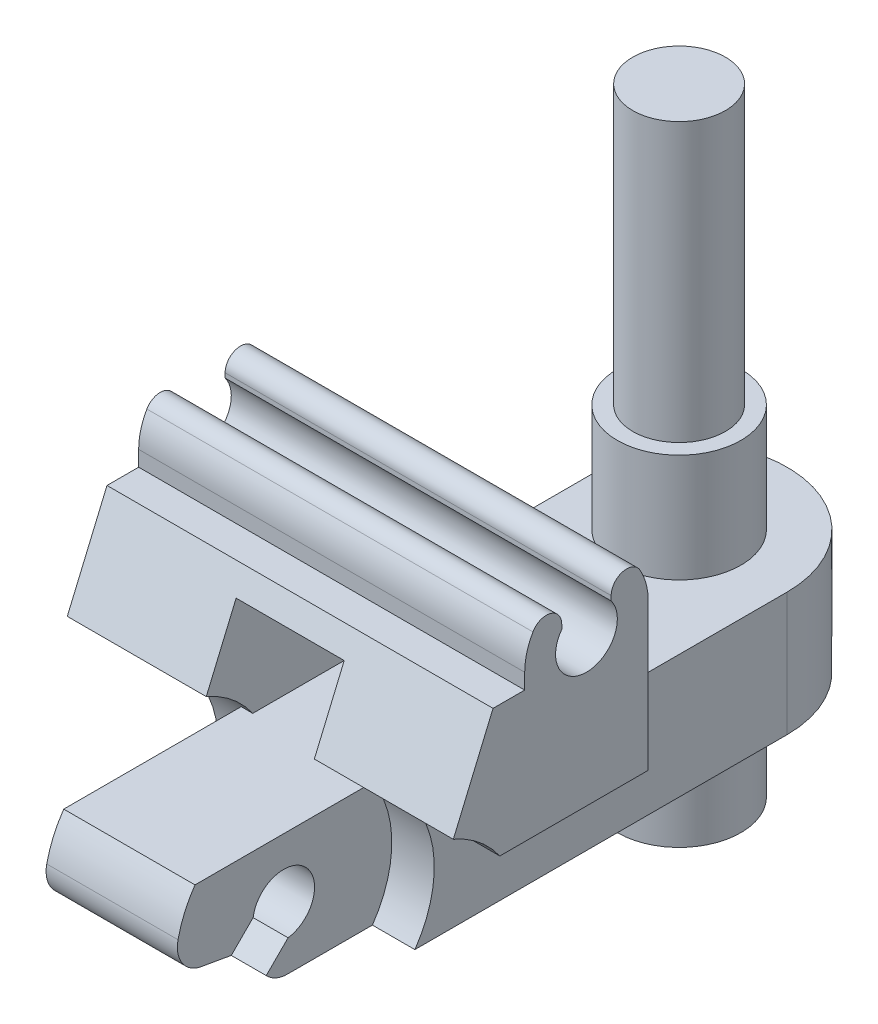
SolidWorks part; units mm, degrees
ref_plane "Front Plane" through (0, 0, 0) normal (0, 0, 1) x (1, 0, 0)
ref_plane "Top Plane" through (0, 0, 0) normal (0, 1, 0) x (1, 0, 0)
ref_plane "Right Plane" through (0, 0, 0) normal (1, 0, 0) x (0, 0, -1)
sketch "Sketch3" plane through (0, 0, 0) normal (1, 0, 0) x (0, 0, -1)
  line L0 (0.2828, -1.9799) -> (-1.9799, 0.2828)
  line L1 (0.2828, -1.9799) -> (-1.1314, -3.3941)
  line L2 (-1.1314, -3.3941) -> (-0.8188, -5.1668)
  line L3 (-0.8188, -5.1668) -> (-2.2728, -6.6208)
  line L4 (-1.9799, 0.2828) -> (-3.3941, -1.1314)
  line L5 (-3.3941, -1.1314) -> (-5.1668, -0.8188)
  line L6 (-5.1668, -0.8188) -> (-6.6208, -2.2728)
  line L7 (-0.8485, -0.8485) -> (0, 0) construction
  line L8 (0, 0) -> (-2, 0) construction
  line L9 (-1.9799, 0.2828) -> (-5.1668, -0.8188) construction
  line L10 (-0.8188, -5.1668) -> (0.2828, -1.9799) construction
  circle A0 centre (0, 0) radius 2
  circle A1 centre (0, 0) radius 6 construction
  circle A2 centre (0, 0) radius 6.5 construction
  circle A3 centre (0, 0) radius 7
  dimension "D1" = 4
  dimension "D2" = 12
  dimension "D3" = 5
  dimension "D4" = 0.5
  dimension "D5" = 2
  dimension "D7" = 3.2
  dimension "D6" = 1.8
  dimension "D8" = 45
  dimension "D9" = 125
extrude "Boss-Extrude1" add sketch "Sketch3" along normal mid plane 8.5 contours A3 L6 L5 L4 A0 L1 L2 L3 | A3 region at (0, -1.4401, -1.6605)
sketch "Sketch5" plane through (0, 0, 0) normal (1, 0, 0) x (0, 0, -1)
  line L0 (0, 7) -> (29.856, 7)
  line L1 (29.856, 7) -> (29.856, -7)
  line L2 (29.856, -7) -> (0, -7)
  arc A0 (-2.2728, -6.6208) -> (-6.6208, -2.2728) centre (0, 0) ccw construction
  arc A1 (0, -7) -> (0, 7) centre (0, 0) ccw
  dimension "D1" = 29.856
extrude "Boss-Extrude2" add sketch "Sketch5" along normal mid plane 14
sketch "Sketch6" plane through (0, 7, 0) normal (0, 1, 0) x (1, 0, 0)
  line L0 (7, 29.856) -> (-7, 29.856) construction
  circle A0 centre (0, 29.856) radius 7
extrude "Boss-Extrude3" add sketch "Sketch6" against normal up to surface (14 mm away) up to face at (0, -7, -9.952)
sketch "Sketch7" plane through (0, 0, 0) normal (0, 1, 0) x (1, 0, 0)
  circle A0 centre (0, 29.856) radius 4
  dimension "D1" = 8
extrude "Boss-Extrude4" add sketch "Sketch7" along normal blind 11 and the other way blind 11
sketch "Sketch22" plane through (0, 11, 0) normal (0, 1, 0) x (1, 0, 0)
  circle A0 centre (0, 29.856) radius 3
  dimension "D1" = 6
extrude "Boss-Extrude6" add sketch "Sketch22" along normal blind 18
sketch "Sketch8" plane through (0, 7, 0) normal (0, 1, 0) x (1, 0, 0)
  line L0 (4.25, -7) -> (4.25, 0) construction
  line L1 (-4.25, 0) -> (-4.25, -7) construction
  line L3 (7, 0) -> (7, 29.856) construction
  line L4 (-7, 29.856) -> (-7, 0) construction
  line L5 (-7, 0) -> (-4.25, 0) construction
  line L6 (4.25, 0) -> (7, 0) construction
  line L7 (4.25, -7) -> (4.25, 0)
  line L8 (-4.25, 0) -> (-4.25, -7)
  line L9 (-4.25, -7) -> (4.25, -7)
  line L10 (7, 0) -> (7, 29.856)
  line L11 (-7, 29.856) -> (-7, 0)
  line L12 (-7, 0) -> (-4.25, 0)
  line L13 (4.25, 0) -> (7, 0)
  arc A0 (7, 29.856) -> (-7, 29.856) centre (0, 29.856) ccw construction
  arc A1 (7, 29.856) -> (-7, 29.856) centre (0, 29.856) ccw
  circle M9 centre (0, 29.856) radius 4
  line M10 (7, 0) -> (7, 29.856)
  arc M11 (7, 29.856) -> (-7, 29.856) centre (0, 29.856) ccw
  line M12 (-7, 29.856) -> (-7, 0)
  line M13 (-7, 0) -> (-4.25, 0)
  line M14 (-4.25, 0) -> (4.25, 0)
  line M15 (4.25, 0) -> (7, 0)
extrude "Cut-Extrude2" cut sketch "Sketch8" against normal offset from surface (3 mm away) 4 contours M15 M10 M11 M12 M13 M14 M9 | L8 L9 L7 M14 region at (0, 7, 3.5) region at (0, 7, -16.3386) up to plane "Top Plane"
sketch "Sketch9" plane through (0, -7, 0) normal (0, -1, 0) x (1, 0, 0)
  line L7 (4.25, 0) -> (4.25, 7)
  line L8 (7, 0) -> (4.25, 0)
  line L9 (7, -29.856) -> (7, 0)
  line L10 (-7, 0) -> (-7, -29.856)
  line L11 (-4.25, 0) -> (-7, 0)
  line L12 (-4.25, 7) -> (-4.25, 0)
  line L13 (4.25, 7) -> (-4.25, 7)
  line L14 (4.25, 0) -> (4.25, 7)
  line L15 (7, 0) -> (4.25, 0)
  line L16 (7, -29.856) -> (7, 0)
  line L17 (-7, 0) -> (-7, -29.856)
  line L18 (-4.25, 0) -> (-7, 0)
  line L19 (-4.25, 7) -> (-4.25, 0)
  line L20 (4.25, 7) -> (-4.25, 7)
  arc A1 (-7, -29.856) -> (7, -29.856) centre (0, -29.856) ccw
  arc A2 (-7, -29.856) -> (7, -29.856) centre (0, -29.856) ccw
  circle M9 centre (0, -29.856) radius 4
  line M10 (-7, 0) -> (-7, -29.856)
  arc M11 (-7, -29.856) -> (7, -29.856) centre (0, -29.856) ccw
  line M12 (7, -29.856) -> (7, 0)
  line M13 (7, 0) -> (4.25, 0)
  line M14 (4.25, 0) -> (-4.25, 0)
  line M15 (-4.25, 0) -> (-7, 0)
  dimension "D1" = 0
extrude "Cut-Extrude4" cut sketch "Sketch9" against normal offset from surface (3 mm away) 4 contours M15 M10 M11 M12 M13 M14 M9 | L14 L20 L19 M14 region at (0, -7, 3.5) region at (0, -7, -16.3386) up to plane "Top Plane"
sketch "Sketch10" plane through (0, 0, 0) normal (1, 0, 0) x (0, 0, -1)
  line L3 (5.7446, -4) -> (29.856, -4)
  line L4 (29.856, -4) -> (29.856, 4)
  line L5 (29.856, 4) -> (5.7446, 4)
  line L10 (7.356, 12.5) -> (7.356, 17.5) construction
  line L11 (7.356, 17.5) -> (15.356, 17.5) construction
  line L12 (15.356, 17.5) -> (15.356, 4) construction
  line L13 (5.3059, 12.5) -> (7.356, 12.5)
  line L14 (0, 0) -> (2.7351, 6.4435) construction
  line L15 (2.7351, 6.4435) -> (5.3059, 12.5)
  line L16 (29.856, 4) -> (5.7446, 4) construction
  line L17 (15.356, 4) -> (5.7446, 4)
  line L18 (7.356, 13.5) -> (15.356, 13.5) construction
  line L19 (29.856, 11) -> (29.856, 4) construction
  line L20 (33.856, 11) -> (25.856, 11) construction
  line L21 (9.756, 14.7) -> (12.956, 14.7) construction
  line L22 (12.956, 14.7) -> (12.956, 17.1661)
  line L23 (9.756, 17.1661) -> (9.756, 14.7)
  line L24 (7.356, 13.5) -> (7.356, 12.5)
  line L25 (15.356, 13.5) -> (15.356, 4)
  arc A0 (9.756, 14.7) -> (12.956, 14.7) centre (11.356, 13.5) ccw
  arc A1 (5.7446, -4) -> (5.7446, 4) centre (0, 0) ccw
  arc A2 (5.7446, 4) -> (2.7351, 6.4435) centre (0, 0) ccw
  arc A3 (15.356, 13.5) -> (12.956, 17.1661) centre (11.356, 13.5) ccw
  arc A4 (9.756, 17.1661) -> (7.356, 13.5) centre (11.356, 13.5) ccw
  dimension "D8" = 4
  dimension "D9" = 2
  dimension "D10" = 3.2
  dimension "D2" = 67
  dimension "D3" = 14.5
  dimension "D4" = 13.5
  dimension "D5" = 5
  dimension "D7" = 5
  dimension "D1" = 0
extrude "Boss-Extrude5" add sketch "Sketch10" along normal mid plane 25
ref_plane "Plane1" through (6, 0, 0) normal (1, 0, 0) x (0, 0, -1)
ref_plane "Plane2" through (-6, 0, 0) normal (1, 0, 0) x (0, 0, -1)
sketch "Sketch13" plane through (-6, 0, 0) normal (1, 0, 0) x (0, 0, -1)
  line L0 (0, 5) -> (33.856, 5)
  line L1 (33.856, 4) -> (33.856, 11) construction
  circle A0 centre (0, 0) radius 5 construction
  dimension "D1" = 10
ref_plane "Plane3" through (0, 0, 0) normal (0, 0, 1) x (1, 0, 0)
sketch "Sketch14" plane through (0, 0, 0) normal (0, 0, 1) x (1, 0, 0)
  line L0 (-6.5303, 5.5303) -> (-8.0607, 4)
  line L1 (-7, 4) -> (-12.5, 4) construction
  line L2 (-5.4697, 4.4697) -> (-7, 2.9393)
  line L3 (-7, 4) -> (-7, -4) construction
  line L4 (-6.5303, 5.5303) -> (-5.4697, 4.4697) construction
  line L5 (-8.0607, 4) -> (-7, 4)
  line L6 (-7, 4) -> (-7, 2.9393)
  arc A0 (-5.4697, 4.4697) -> (-6.5303, 5.5303) centre (-6, 5) ccw
  point P14 (-6, 5)
  dimension "D1" = 1.5
  dimension "D2" = 45
sweep "Cut-Sweep1" cut profiles "Sketch14" path "Sketch13"
ref_plane "Plane4" through (0, 0, -32.856) normal (0, 0, -1) x (-1, 0, 0)
ref_plane "Plane5" through (-3, 0, 0) normal (-1, 0, 0) x (0, 0, 1)
sketch "Sketch18" plane through (0, 0, -32.856) normal (0, 0, -1) x (-1, 0, 0)
  line L0 (0, 29) -> (0, 16) construction
  line L2 (3, 29) -> (-3, 29) construction
  circle A0 centre (0, 16) radius 1.9
  point P2 (0, 26)
  point P6 (0, 0)
  point P7 (0, 0)
  dimension "D2" = 3.8
  dimension "D1" = 13
extrude "Cut-Extrude5" cut sketch "Sketch18" against normal blind 1
sketch "Sketch20" plane through (0, 11, 0) normal (0, 1, 0) x (1, 0, 0)
  line L0 (0, 25.856) -> (0, 0) construction
  line L2 (-3.5, -15.356) -> (3.5, -15.356)
  line L3 (-3.5, -15.356) -> (-3.5, 15.356)
  line L4 (-3.5, 15.356) -> (3.5, 15.356)
  line L5 (3.5, -15.356) -> (3.5, 15.356)
  line L6 (-3.5, -15.356) -> (3.5, 15.356) construction
  line L7 (-3.5, 15.356) -> (3.5, -15.356) construction
  line L8 (-5.9393, 15.356) -> (7, 15.356) construction
  circle A0 centre (0, 29.856) radius 4 construction
  circle A1 centre (0, 29.856) radius 4 construction
  dimension "D1" = 7
extrude "Cut-Extrude7" cut sketch "Sketch20" against normal up to surface (7 mm away) up to face at (0, 4, 0)
fillet "Fillet1" radius 1.9 2 edges at (0, -2.2728, 6.6208) (0, -4, 1.0245)
fillet "Fillet2" radius 1 2 edges at (0, 17.1661, -12.956) (0, 17.1661, -9.756)
